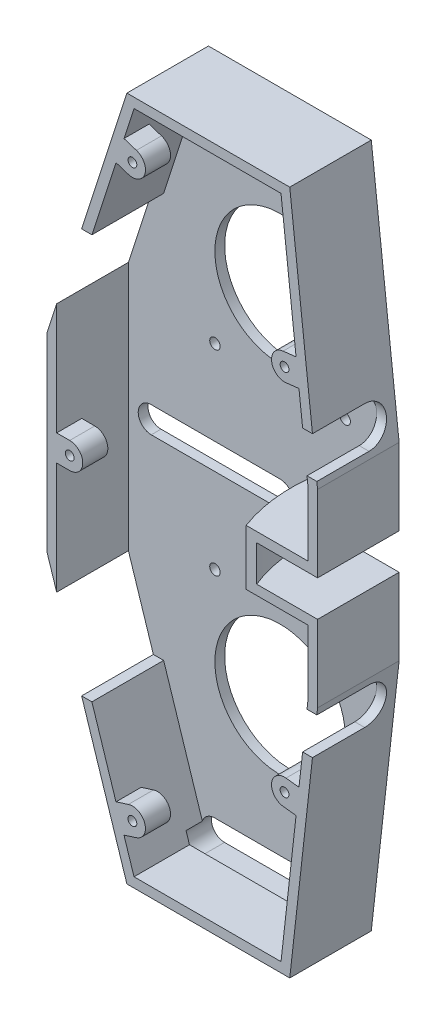
SolidWorks part; units mm, degrees
material "ABS"
ref_plane "Front Plane" through (0, 0, 0) normal (0, 0, 1) x (1, 0, 0)
ref_plane "Top Plane" through (0, 0, 0) normal (0, 1, 0) x (1, 0, 0)
ref_plane "Right Plane" through (0, 0, 0) normal (1, 0, 0) x (0, 0, -1)
sketch "Sketch2" plane through (0, 0, 0) normal (0, 0, 1) x (1, 0, 0)
  line L0 (24.9678, -105) -> (33.5, -29) construction
  line L1 (33.5, 5) -> (33.5, 29) construction
  line L2 (33.5, 29) -> (24.9678, 105) construction
  line L3 (24.9678, -105) -> (33.5, -29)
  line L4 (33.5, -29) -> (33.5, 29)
  line L5 (33.5, 29) -> (24.9678, 105)
  line L12 (-49.5, -29) -> (-24.9678, -105)
  line L13 (-24.9678, -105) -> (24.9678, -105)
  line L14 (24.9678, -105) -> (33.5, -29)
  line L15 (33.5, -29) -> (33.5, -5)
  line L16 (33.5, -5) -> (13.9678, -5)
  line L17 (13.9678, -5) -> (13.9678, 5)
  line L18 (13.9678, 5) -> (33.5, 5)
  line L19 (33.5, 5) -> (33.5, 29)
  line L20 (33.5, 29) -> (24.9678, 105)
  line L21 (24.9678, 105) -> (-24.9678, 105)
  line L22 (-24.9678, 105) -> (-49.5, 29)
  line L23 (-49.5, 29) -> (-49.5, -29)
  line L24 (-49.5, -29) -> (-24.9678, -105)
  line L25 (-24.9678, -105) -> (24.9678, -105)
  line L33 (24.9678, 105) -> (-24.9678, 105)
  line L34 (-24.9678, 105) -> (-49.5, 29)
  line L35 (-49.5, 29) -> (-49.5, -29)
  dimension "D1" = 0
extrude "Extrude1" add sketch "Sketch2" along normal blind 40
chamfer "Chamfer1" distance 20 angle 30 8 edges at (33.5, 0, 40) (29.2339, -67, 40) (29.2339, 67, 40) (0, 105, 40) (0, -105, 40) (-37.2339, -67, 40) (-37.2339, 67, 40) (-49.5, 0, 40) first distance on face at (-4, 0, 40)
sketch "Sketch4" plane through (0, -2.5, 0) normal (0, -1, 0) x (1, 0, 0)
  circle A0 centre (56.5, 8) radius 45
  dimension "D1" = 90
extrude "Cut-Extrude1" cut sketch "Sketch4" against normal blind 8 and the other way blind 3
shell "Shell2" thickness 3 removed face at (-4.83, 0, 40)
sketch "Sketch6" plane through (0, 0, 40) normal (0, 0, 1) x (1, 0, 0)
  line L1 (-57.1805, 105.989) -> (68.2016, 105.989)
  line L2 (-57.1805, 105.989) -> (-57.1805, -156.9729)
  line L3 (-57.1805, -156.9729) -> (68.2016, -156.9729)
  line L4 (68.2016, 105.989) -> (68.2016, -156.9729)
extrude "Cut-Extrude3" cut sketch "Sketch6" against normal blind 15
sketch "Sketch7" plane through (0, 0, 25) normal (0, 0, 1) x (1, 0, 0)
  line L0 (30.5, 8.5) -> (30.5, 28.8321) construction
  line L1 (8.5, 62) -> (-46.5, 62)
  line L2 (8.5, 62) -> (8.5, -62)
  line L3 (8.5, -62) -> (-46.5, -62)
  line L4 (-46.5, 62) -> (-46.5, -62)
  line L5 (-46.5, 28.5278) -> (-46.5, -28.5278) construction
  line L6 (22.2857, 102) -> (-22.7837, 102) construction
  line L7 (-22.7837, -102) -> (22.2857, -102) construction
  dimension "D1" = 22
  dimension "D2" = 40
  dimension "D3" = 40
extrude "Cut-Extrude4" cut sketch "Sketch7" against normal up to vertex (22 mm away) up to point (-46.5, -28.5278, 3)
sketch "Sketch8" plane through (0, 0, 3) normal (0, 0, 1) x (1, 0, 0)
  line L0 (-20.0322, 100) -> (19.9678, 100) construction
  line L1 (-20.0322, 104) -> (19.9678, 104)
  line L2 (-20.0322, 96) -> (19.9678, 96)
  line L3 (-20.0322, -100) -> (19.9678, -100) construction
  line L4 (-20.0322, -96) -> (19.9678, -96)
  line L5 (-20.0322, -104) -> (19.9678, -104)
  line L6 (-39.5, 0) -> (0, 0) construction
  line L7 (-39.5, 4) -> (0, 4)
  line L8 (-39.5, -4) -> (0, -4)
  arc A0 (-20.0322, 104) -> (-20.0322, 96) centre (-20.0322, 100) ccw
  arc A1 (19.9678, 96) -> (19.9678, 104) centre (19.9678, 100) ccw
  arc A2 (-20.0322, -96) -> (-20.0322, -104) centre (-20.0322, -100) ccw
  arc A3 (19.9678, -104) -> (19.9678, -96) centre (19.9678, -100) ccw
  circle A4 centre (0, 54.5) radius 20
  circle A5 centre (0, -54.5) radius 20
  arc A6 (-39.5, 4) -> (-39.5, -4) centre (-39.5, 0) ccw
  arc A7 (0, -4) -> (0, 4) centre (0, 0) ccw
  circle A8 centre (19.9678, -30) radius 1.6 construction
  circle A9 centre (-19.9678, -30) radius 1.6 construction
  circle A10 centre (19.9678, 30) radius 1.6 construction
  circle A11 centre (-19.9678, 30) radius 1.6 construction
  circle A12 centre (19.9678, -30) radius 1.6
  circle A13 centre (-19.9678, -30) radius 1.6
  circle A14 centre (19.9678, 30) radius 1.6
  circle A15 centre (-19.9678, 30) radius 1.6
  point P4 (-0.0322, 100)
  point P13 (-0.0322, -100)
  point P28 (-19.75, 0)
  dimension "D1" = 4
  dimension "D2" = 4
  dimension "D3" = 40
  dimension "D4" = 4
extrude "Cut-Extrude5" cut sketch "Sketch8" against normal blind 12 and the other way blind 5
sketch "Sketch9" plane through (33.5, 0, 0) normal (1, 0, 0) x (0, 0, -1)
  line L0 (-25, 37) -> (-9, 37) construction
  line L1 (-25, 29) -> (-25, 105) construction
  line L2 (-25, 43) -> (-9, 43)
  line L3 (-25, 31) -> (-9, 31)
  line L4 (-25, -37) -> (-9, -37) construction
  line L5 (-25, -105) -> (-25, -29) construction
  line L6 (-25, -31) -> (-9, -31)
  line L7 (-25, -43) -> (-9, -43)
  line L8 (-25, -29) -> (0, -29) construction
  line L9 (-25, 29) -> (0, 29) construction
  arc A0 (-25, 43) -> (-25, 31) centre (-25, 37) ccw
  arc A1 (-9, 31) -> (-9, 43) centre (-9, 37) ccw
  arc A2 (-25, -31) -> (-25, -43) centre (-25, -37) ccw
  arc A3 (-9, -43) -> (-9, -31) centre (-9, -37) ccw
  point P4 (-17, 37)
  point P9 (-17, -37)
  dimension "D3" = 6
  dimension "D4" = 6
  dimension "D1" = 16
  dimension "D2" = 16
  dimension "D5" = 8
  dimension "D6" = 8
extrude "Cut-Extrude6" cut sketch "Sketch9" against normal blind 10
sketch "Sketch10" plane through (0, 0, 25) normal (0, 0, 1) x (1, 0, 0)
  line L0 (-25.8556, 92.4835) -> (-28.3131, 84.8703)
  line L1 (-25.8556, 92.4835) -> (-22.049, 91.2548)
  line L2 (-28.3131, 84.8703) -> (-24.5065, 83.6416)
  line L4 (-23.8324, 98.7514) -> (-35.6954, 62) construction
  line L5 (-46.5, 4) -> (-46.5, -4)
  line L6 (-46.5, 4) -> (-42.5, 4)
  line L7 (-46.5, -4) -> (-42.5, -4)
  line L9 (-46.5, 38.2939) -> (-46.5, -38.2939) construction
  line L14 (27.7938, -52.9376) -> (23.8187, -52.4913)
  line L15 (26.9013, -60.8876) -> (22.9262, -60.4414)
  line L16 (26.9013, 60.8876) -> (27.7938, 52.9376)
  line L17 (26.9013, 60.8876) -> (22.9262, 60.4414)
  line L18 (27.7938, 52.9376) -> (23.8187, 52.4913)
  line L20 (29.583, 37) -> (22.8246, 97.2002) construction
  line L25 (26.9013, -60.8876) -> (27.7938, -52.9376)
  line L26 (-46.5, 0) -> (29.1357, 0) construction
  line L27 (-46.5, 38.2939) -> (-46.5, -38.2939) construction
  line L28 (-28.3131, -84.8703) -> (-24.5065, -83.6416)
  line L29 (-25.8556, -92.4835) -> (-22.049, -91.2548)
  line L30 (-25.8556, -92.4835) -> (-28.3131, -84.8703)
  arc A0 (-22.049, 91.2548) -> (-24.5065, 83.6416) centre (-23.2777, 87.4482) cw
  arc A1 (22.9262, 60.4414) -> (23.8187, 52.4913) centre (23.3725, 56.4663) ccw
  arc A2 (-42.5, 4) -> (-42.5, -4) centre (-42.5, 0) cw
  circle A3 centre (-23.2777, 87.4482) radius 1.35
  circle A4 centre (23.3725, 56.4663) radius 1.35
  circle A5 centre (-42.5, 0) radius 1.35
  circle A6 centre (23.3725, -56.4663) radius 1.35
  circle A7 centre (-23.2777, -87.4482) radius 1.35
  arc A8 (22.9262, -60.4414) -> (23.8187, -52.4913) centre (23.3725, -56.4663) cw
  arc A9 (-22.049, -91.2548) -> (-24.5065, -83.6416) centre (-23.2777, -87.4482) ccw
  dimension "D1" = 4
  dimension "D3" = 2.7
  dimension "D2" = 4
  dimension "D4" = 10
  dimension "D5" = 10
extrude "Extrude2" add sketch "Sketch10" against normal blind 10
chamfer "Chamfer2" distance 4 angle 30 15 edges at (24.9137, 60.6645, 15) (19.3975, 56.0201, 15) (25.8063, 52.7144, 15) (-44.5, 4, 15) (-38.5, 0, 15) (-44.5, -4, 15) (-23.9523, 91.8691, 15) (-19.4711, 86.2194, 15) (-26.4098, 84.2559, 15) (-26.4098, -84.2559, 15) (-19.4711, -86.2194, 15) (-23.9523, -91.8691, 15) (25.8063, -52.7144, 15) (19.3975, -56.0201, 15) (24.9137, -60.6645, 15) first distance on face at (24.7225, 56.4663, 15) first distance on face at (-41.15, 0, 15) first distance on face at (-21.9277, 87.4482, 15) first distance on face at (-24.6277, -87.4482, 15) first distance on face at (22.0225, -56.4663, 15)
